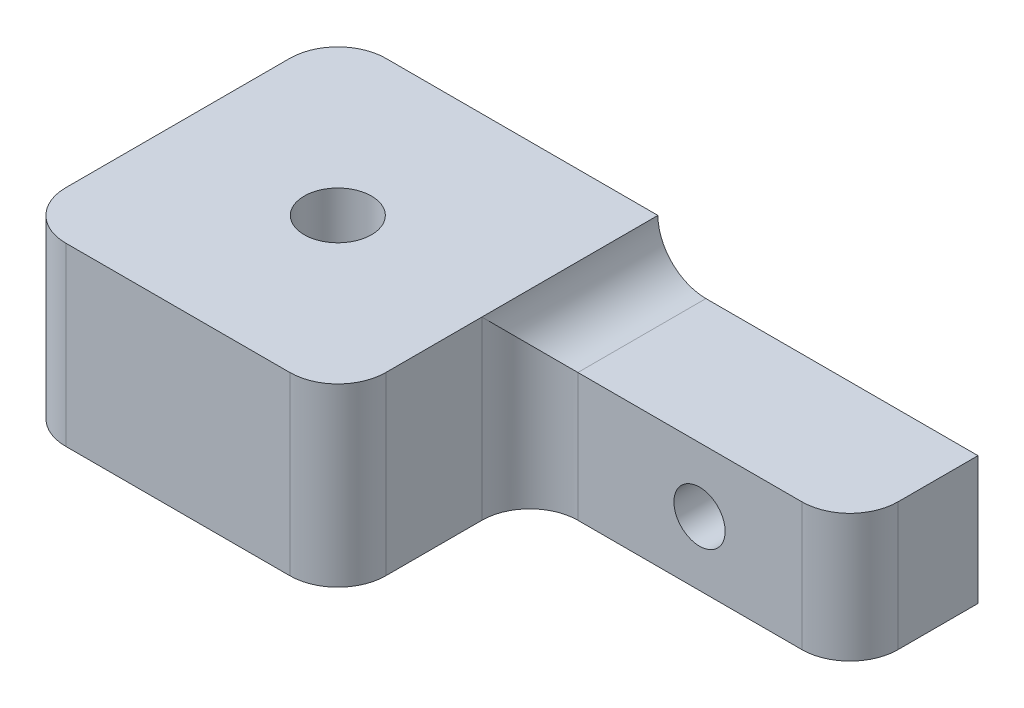
SolidWorks part; units mm, degrees
ref_plane "Plan de face" through (0, 0, 0) normal (0, 0, 1) x (1, 0, 0)
ref_plane "Plan de dessus" through (0, 0, 0) normal (0, 1, 0) x (1, 0, 0)
ref_plane "Plan de droite" through (0, 0, 0) normal (1, 0, 0) x (0, 0, -1)
sketch "Esquisse1" plane through (0, 0, 0) normal (0, 0, 1) x (1, 0, 0)
  line L1 (0, 0) -> (40, 0)
  line L2 (0, 0) -> (0, 8)
  line L3 (0, 8) -> (40, 8)
  line L4 (40, 0) -> (40, 8)
  dimension "D1" = 40
  dimension "D2" = 8
extrude "Boss.-Extru.1" add sketch "Esquisse1" along normal blind 8
sketch "Esquisse2" plane through (0, 0, 8) normal (0, 0, 1) x (1, 0, 0)
  line L0 (0, 0) -> (40, 0) construction
  line L1 (0, 8) -> (20, 8)
  line L2 (0, 8) -> (0, 0)
  line L3 (0, 0) -> (20, 0)
  line L4 (20, 8) -> (20, 0)
  dimension "D1" = 20
extrude "Boss.-Extru.2" add sketch "Esquisse2" along normal blind 12
sketch "Esquisse3" plane through (0, 8, 0) normal (0, 1, 0) x (1, 0, 0)
  line L0 (40, 0) -> (0, 0) construction
  line L1 (0, -20) -> (20, -20)
  line L2 (0, -20) -> (0, 0)
  line L3 (0, 0) -> (20, 0)
  line L4 (20, -20) -> (20, 0)
extrude "Boss.-Extru.3" add sketch "Esquisse3" along normal blind 3
fillet "Congé1" radius 3 6 edges at (20, 5.5, 20) (40, 4, 8) (0, 5.5, 0) (0, 5.5, 20)
sketch "Esquisse4" plane through (0, 0, 0) normal (0, 0, -1) x (-1, 0, 0)
  line L0 (0, 11) -> (0, 0) construction
  line L1 (-3, 0) -> (-40, 0) construction
  circle A0 centre (-30.6, 4) radius 1.6
  dimension "D3" = 3.2
  dimension "D1" = 30.6
  dimension "D2" = 4
extrude "Enlèv. mat.-Extru.1" cut sketch "Esquisse4" against normal through all
sketch "Esquisse5" plane through (0, 0, 0) normal (0, -1, 0) x (1, 0, 0)
  line L0 (3, 20) -> (17, 20) construction
  line L1 (0, 17) -> (0, 3) construction
  circle A0 centre (10, 10) radius 2.1
  dimension "D3" = 4.2
  dimension "D1" = 10
  dimension "D2" = 10
extrude "Enlèv. mat.-Extru.2" cut sketch "Esquisse5" against normal through all
